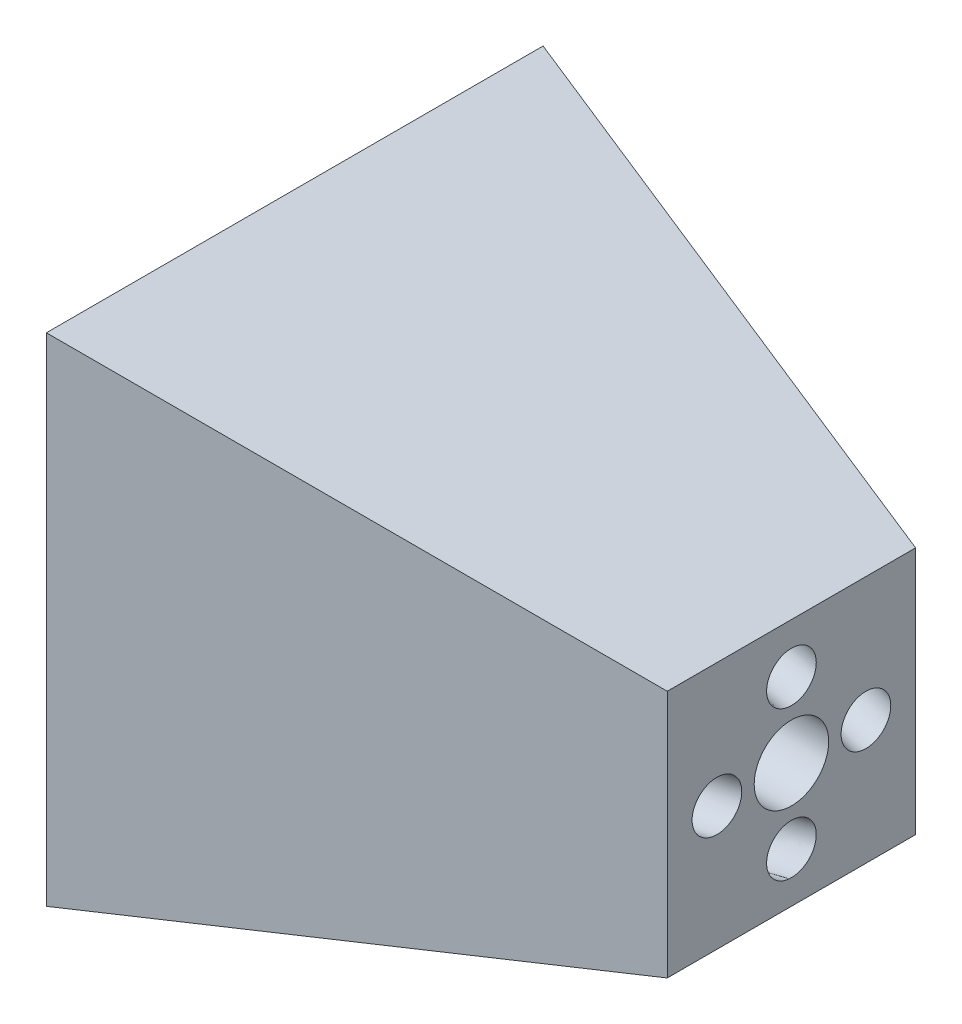
SolidWorks part; units mm, degrees
ref_plane "Front Plane" through (0, 0, 0) normal (0, 0, 1) x (1, 0, 0)
ref_plane "Top Plane" through (0, 0, 0) normal (0, 1, 0) x (1, 0, 0)
ref_plane "Right Plane" through (0, 0, 0) normal (1, 0, 0) x (0, 0, -1)
sketch "Sketch1" plane through (0, 0, 0) normal (1, 0, 0) x (0, 0, -1)
  line L1 (1270, 1270) -> (-1270, 1270)
  line L2 (1270, 1270) -> (1270, -1270)
  line L3 (1270, -1270) -> (-1270, -1270)
  line L4 (-1270, 1270) -> (-1270, -1270)
  line L5 (1270, 1270) -> (-1270, -1270) construction
  line L6 (1270, -1270) -> (-1270, 1270) construction
  circle A0 centre (0, -1016) radius 127
  circle A1 centre (0, 0) radius 190.5
  circle A2 centre (-1016, 0) radius 127
  circle A3 centre (0, 1016) radius 127
  circle A4 centre (1016, 0) radius 127
  point P0 (0, 0)
  point P19 (0, 0)
  dimension "D2" = 254
  dimension "D3" = 381
  dimension "D4" = 254
  dimension "D1" = 2540
  dimension "D5" = 4
ref_plane "Plane2" through (2540, 0, 0) normal (1, 0, 0) x (0, 0, -1)
sketch "Sketch2" plane through (2540, 0, 0) normal (1, 0, 0) x (0, 0, -1)
  line L1 (635, 635) -> (-635, 635)
  line L2 (635, 635) -> (635, -635)
  line L3 (635, -635) -> (-635, -635)
  line L4 (-635, 635) -> (-635, -635)
  line L5 (635, 635) -> (-635, -635) construction
  line L6 (635, -635) -> (-635, 635) construction
  circle A0 centre (0, -381) radius 127
  circle A1 centre (-381, 0) radius 127
  circle A2 centre (0, 381) radius 127
  circle A3 centre (381, 0) radius 127
  circle A4 centre (0, 0) radius 190.5
  point P0 (0, 0)
  point P17 (0, 0)
  dimension "D3" = 254
  dimension "D5" = 381
  dimension "D1" = 1270
  dimension "D2" = 254
  dimension "D4" = 4
loft "Loft2" add section "Sketch1" section "Sketch2" connector at (0, 1270, 1270) connector at (2540, 635, 635)
loft "Cut-Loft1" cut section "Sketch2<4>" section "Sketch1<5>" connector at (2540, 11.2366, 507.5019) connector at (0, -35.4319, 1137.9573)
sketch "Sketch2<4>" plane through (2540, 0, 0) normal (1, 0, 0) x (0, 0, -1) same geometry as "Sketch2"
sketch "Sketch1<5>" plane through (0, 0, 0) normal (1, 0, 0) x (0, 0, -1) same geometry as "Sketch1"
sketch "Sketch3" plane through (0, 0, 0) normal (0, 1, 0) x (1, 0, 0)
  line L0 (0, 0) -> (2540, 0) construction
pattern_circular "CirPattern1" count 4 every 90 about axis through (0, 0, 0) along (1, 0, 0) of "Cut-Loft1"
extrude "Cut-Extrude1" cut sketch "Sketch1<6>" along normal through all contours A1
sketch "Sketch1<6>" plane through (0, 0, 0) normal (1, 0, 0) x (0, 0, -1) same geometry as "Sketch1"
